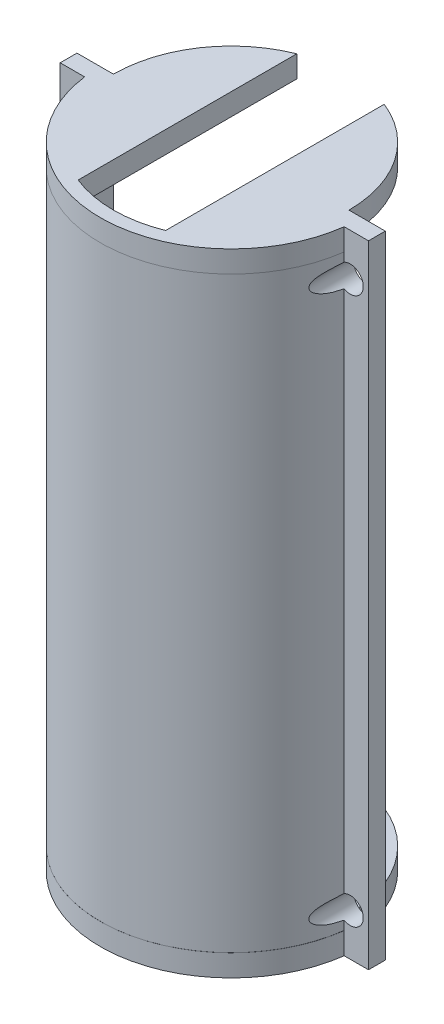
SolidWorks part; units mm, degrees
ref_plane "Front Plane" through (0, 0, 0) normal (0, 0, 1) x (1, 0, 0)
ref_plane "Top Plane" through (0, 0, 0) normal (0, 1, 0) x (1, 0, 0)
ref_plane "Right Plane" through (0, 0, 0) normal (1, 0, 0) x (0, 0, -1)
sketch "Sketch1" plane through (0, 0, 0) normal (0, 1, 0) x (1, 0, 0)
  line L6 (13.4915, 0) -> (17.667, 0)
  line L7 (-17.683, 0) -> (-13.5085, 0)
  line L8 (-17.683, 0) -> (-17.683, -1.9241)
  line L9 (-17.683, -1.9241) -> (-14.8769, -1.9241)
  line L10 (17.667, 0) -> (17.667, -1.9241)
  line L11 (14.86, -1.9241) -> (17.667, -1.9241)
  arc A2 (-13.5085, 0) -> (13.4915, 0) centre (-0.0085, 0) ccw
  arc A3 (-14.8769, -1.9241) -> (14.86, -1.9241) centre (-0.0085, 0) ccw
  point P8 (0, 0)
  point P9 (0, 0)
  point P10 (0, 0)
  point P11 (0, 0)
  point P12 (0, 0)
  point P13 (0, 0)
  point P15 (0, 0)
  point P17 (0, 0)
  point P18 (0, 0)
  point P19 (0, 0)
  point P20 (0, 0)
  point P21 (0, 0)
  point P22 (0, 0)
  point P23 (0, 0)
  point P24 (0, 0)
  point P25 (0, 0)
  point P26 (0, 0)
sketch "Sketch8" plane through (0, 0, 0) normal (0, 1, 0) x (1, 0, 0)
  line L0 (-13.5, 0) -> (-15, 0)
  line L1 (13.4915, 0) -> (15, 0)
  line L2 (13.5, 0) -> (15, 0)
  line L3 (-5.0135, 12.5346) -> (-5.0135, -12.5346)
  line L4 (5.0135, 12.5346) -> (5.0135, -12.5346)
  arc A0 (-15, 0) -> (15, 0) centre (0, 0) ccw
  arc A1 (-5.0135, 12.5346) -> (-13.5, 0) centre (0, 0) ccw
  arc A2 (-5.0135, -12.5346) -> (5.0135, -12.5346) centre (0, 0) ccw
  arc A3 (13.5, 0) -> (5.0135, 12.5346) centre (0, 0) ccw
extrude "Boss-Extrude3" add sketch "Sketch1" along normal blind 72.39
extrude "Boss-Extrude5" add sketch "Sketch8" along normal blind 2.5 contours A3 L4 A2 L3 A1 L0 A0 L1 region at (-10.8416, 0, -7.3403)
extrude "Boss-Extrude6" add sketch "Sketch8<6>" against normal blind 2.5 from surface contours A3 L4 A2 L3 A1 L0 A0 L1 region at (-10.8416, 0, -7.3403) starting at face at (-0.0082, 72.39, 4.2831)
sketch "Sketch8<6>" plane through (0, 0, 0) normal (0, 1, 0) x (1, 0, 0) same geometry as "Sketch8"
hole_wizard "Ø3.0mm Dowel Hole2" positions "Sketch13" profile "Sketch14" hole size "Ø3.0" standard "ANSI Metric" end condition through all
sketch "Sketch13" plane through (0, 0, 0) normal (0, 0, -1) x (-1, 0, 0)
  line L0 (17.683, 72.39) -> (17.683, 0) construction
  line L1 (13.5, 72.39) -> (17.683, 72.39) construction
  point P0 (15.583, 67.54)
  dimension "D1" = 2.1
  dimension "D2" = 4.85
sketch "Sketch14" plane through (-15.583, 67.54, 0) normal (1, 0, 0) x (0, 1, 0)
  line L0 (0, 0) -> (0, 15)
  line L1 (0, 15) -> (1.5, 15)
  line L2 (1.5, 15) -> (1.5, 0)
  line L5 (1.5, 0) -> (0, 0)
  line L11 (0, -6.35) -> (0, 107.95) construction
  dimension "Thru Hole Dia." = 3
  dimension "Thru Hole Depth" = 15
hole_wizard "Ø3.0mm Dowel Hole3" positions "Sketch15" profile "Sketch16" hole size "Ø3.0" standard "ANSI Metric" end condition through all
sketch "Sketch15" plane through (0, 0, 0) normal (0, 0, -1) x (-1, 0, 0)
  line L0 (-17.667, 72.39) -> (-17.667, 0) construction
  line L1 (-17.667, 72.39) -> (-13.5, 72.39) construction
  line L2 (-14.86, 0) -> (-17.667, 0) construction
  line L3 (17.683, 72.39) -> (17.683, 0) construction
  line L4 (17.683, 0) -> (14.8769, 0) construction
  point P0 (-15.567, 67.54)
  point P7 (-15.5835, 72.39)
  point P8 (-15.567, 4.85)
  point P13 (15.583, 4.85)
  dimension "D1" = 2.1
  dimension "D2" = 4.85
  dimension "D3" = 2.1
  dimension "D4" = 4.85
  dimension "D5" = 2.1
  dimension "D6" = 4.85
sketch "Sketch16" plane through (15.567, 67.54, 0) normal (1, 0, 0) x (0, 1, 0)
  line L0 (0, 0) -> (0, 15)
  line L1 (0, 15) -> (1.5, 15)
  line L2 (1.5, 15) -> (1.5, 0)
  line L5 (1.5, 0) -> (0, 0)
  line L11 (0, -6.35) -> (0, 107.95) construction
  dimension "Thru Hole Dia." = 3
  dimension "Thru Hole Depth" = 15
